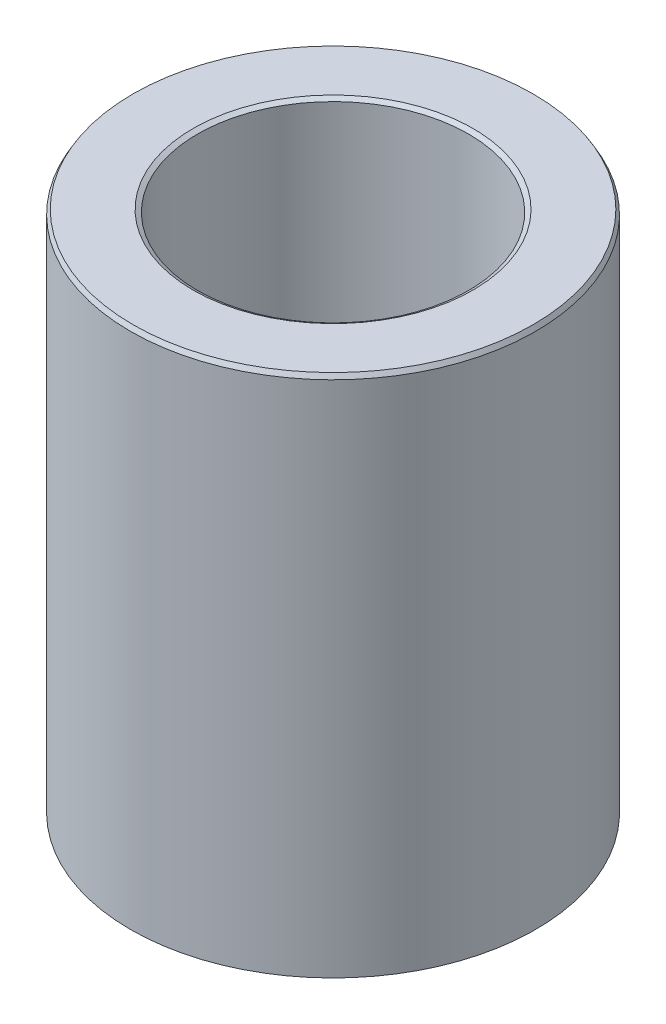
SolidWorks part; units mm, degrees
ref_plane "Front Plane" through (0, 0, 0) normal (0, 0, 1) x (1, 0, 0)
ref_plane "Top Plane" through (0, 0, 0) normal (0, 1, 0) x (1, 0, 0)
ref_plane "Right Plane" through (0, 0, 0) normal (1, 0, 0) x (0, 0, -1)
sketch "Sketch1" plane through (0, 0, 0) normal (0, 1, 0) x (1, 0, 0)
  circle A0 centre (0, 0) radius 40
  dimension "SLEEVE_OD" = 80
extrude "Boss-Extrude1" add sketch "Sketch1" along normal blind 103.689
sketch "Sketch2" plane through (0, 0, 0) normal (0, 1, 0) x (1, 0, 0)
  circle A0 centre (0, 0) radius 26.7669
  dimension "BORE_D" = 53.5337
extrude "Cut-Extrude1" cut sketch "Sketch2" along normal through all
chamfer "Chamfer1" distance 0.8799 angle 30 4 edges at (0, 103.689, 26.7669) (0, 0, 26.7669) (0, 0, 40) (0, 103.689, 40) first distance on face at (0, 103.689, 26.7669) first distance on face at (0, 0, 26.7669) first distance on face at (0, 103.689, 40)
